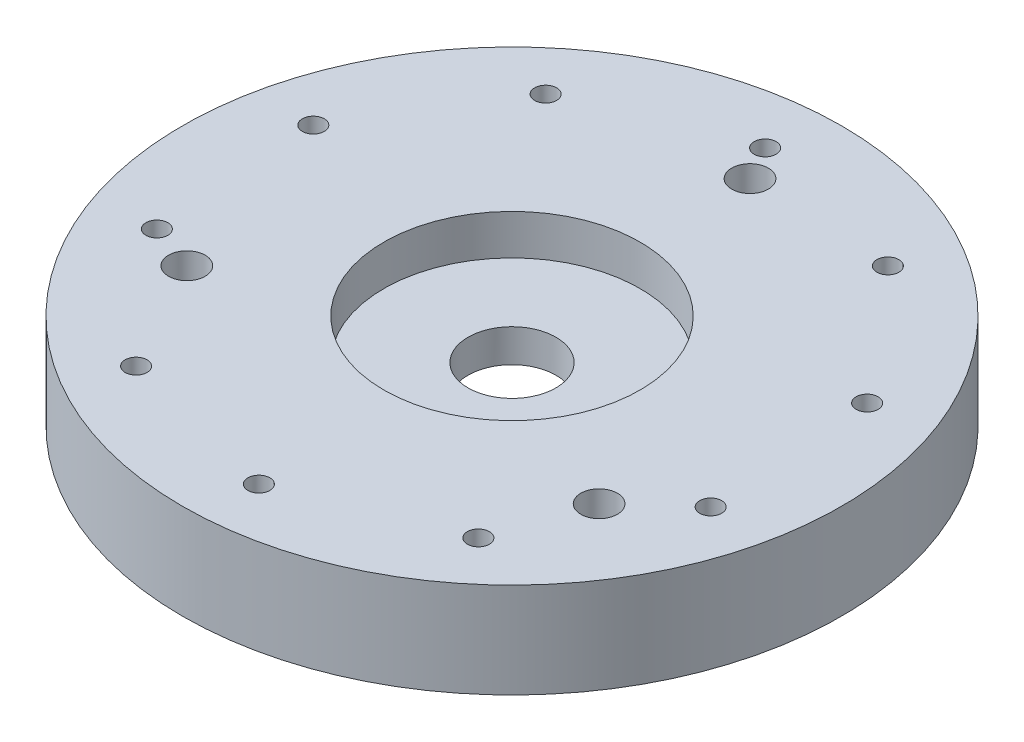
SolidWorks part; units mm, degrees
ref_plane "Front Plane" through (0, 0, 0) normal (0, 0, 1) x (1, 0, 0)
ref_plane "Top Plane" through (0, 0, 0) normal (0, 1, 0) x (1, 0, 0)
ref_plane "Right Plane" through (0, 0, 0) normal (1, 0, 0) x (0, 0, -1)
sketch "Sketch1" plane through (0, 0, 0) normal (0, 1, 0) x (1, 0, 0)
  line L0 (-34.5376, -13.9541) -> (0, 0) construction
  line L1 (-28.1458, -16.25) -> (0, 0) construction
  circle A0 centre (0, 0) radius 45
  circle A1 centre (0, 32.5) radius 2.5
  circle A2 centre (0, 0) radius 32.5 construction
  circle A3 centre (28.1458, -16.25) radius 2.5
  circle A4 centre (-28.1458, -16.25) radius 2.5
  circle A5 centre (0, 0) radius 37.25 construction
  circle A6 centre (-34.5376, -13.9541) radius 1.5
  circle A7 centre (-36.1435, 9.0116) radius 1.5
  circle A8 centre (-23.9438, 28.5352) radius 1.5
  circle A9 centre (-2.5984, 37.1593) radius 1.5
  circle A10 centre (19.7395, 31.5898) radius 1.5
  circle A11 centre (34.5376, 13.9541) radius 1.5
  circle A12 centre (36.1435, -9.0116) radius 1.5
  circle A13 centre (23.9438, -28.5352) radius 1.5
  circle A14 centre (2.5984, -37.1593) radius 1.5
  circle A15 centre (-19.7395, -31.5898) radius 1.5
  point P12 (0, 0)
  point P15 (0, 0)
  point P16 (0, 0)
  point P34 (0, 0)
  dimension "D1" = 90
  dimension "D2" = 65
  dimension "D3" = 5
  dimension "D5" = 74.5
  dimension "D6" = 3
  dimension "D7" = 8
  dimension "D4" = 3
  dimension "D8" = 10
extrude "Boss-Extrude1" add sketch "Sketch1" along normal blind 13
sketch "Sketch2" plane through (0, 13, 0) normal (0, 1, 0) x (1, 0, 0)
  circle A0 centre (0, 0) radius 17.5
  dimension "D1" = 35
extrude "Cut-Extrude1" cut sketch "Sketch2" against normal blind 5.5
sketch "Sketch3" plane through (0, 7.5, 0) normal (0, 1, 0) x (1, 0, 0)
  circle A0 centre (0, 0) radius 6
  dimension "D1" = 12
extrude "Cut-Extrude2" cut sketch "Sketch3" against normal through all
sketch "Sketch4" plane through (0, 0, 0) normal (0, -1, 0) x (1, 0, 0)
  circle A0 centre (0, 0) radius 28.5
  dimension "D1" = 57
extrude "Cut-Extrude3" cut sketch "Sketch4" against normal blind 3
